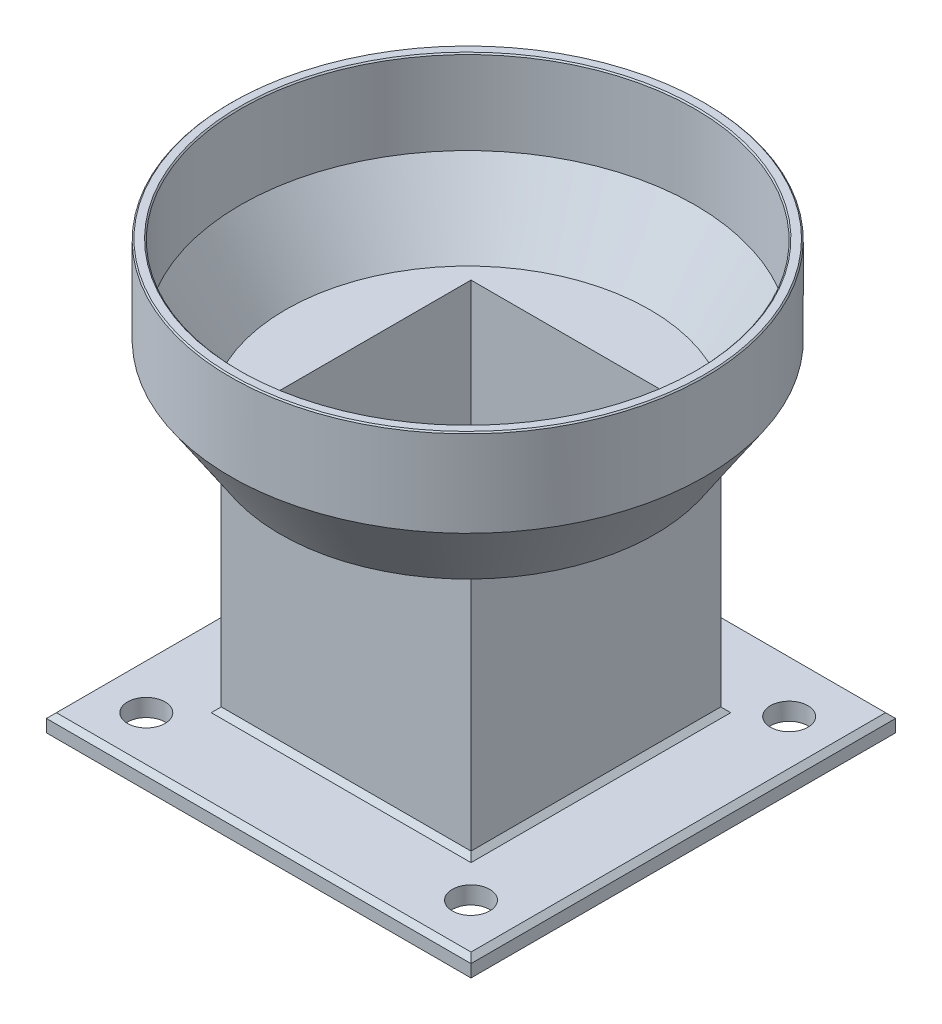
SolidWorks part; units mm, degrees
ref_plane "Plan de face" through (0, 0, 0) normal (0, 0, 1) x (1, 0, 0)
ref_plane "Plan de dessus" through (0, 0, 0) normal (0, 1, 0) x (1, 0, 0)
ref_plane "Plan de droite" through (0, 0, 0) normal (1, 0, 0) x (0, 0, -1)
sketch "Esquisse1" plane through (0, 0, 0) normal (0, 1, 0) x (1, 0, 0)
  line L13 (-124.8507, 26.306) -> (45.1493, 26.306)
  line L14 (-124.8507, 26.306) -> (-124.8507, -143.694)
  line L15 (-124.8507, -143.694) -> (45.1493, -143.694)
  line L16 (45.1493, 26.306) -> (45.1493, -143.694)
  dimension "D1" = 170
  dimension "D2" = 170
extrude "Boss.-Extru.1" add sketch "Esquisse1" along normal blind 7
sketch "Esquisse2" plane through (0, 7, 0) normal (0, 1, 0) x (1, 0, 0)
  line L0 (-124.8507, 26.306) -> (-124.8507, -143.694) construction
  line L1 (-89.8507, -8.694) -> (10.1493, -8.694)
  line L2 (-89.8507, -8.694) -> (-89.8507, -108.694)
  line L3 (-89.8507, -108.694) -> (10.1493, -108.694)
  line L4 (10.1493, -8.694) -> (10.1493, -108.694)
  line L5 (45.1493, 26.306) -> (-124.8507, 26.306) construction
  dimension "D1" = 100
  dimension "D2" = 100
  dimension "D3" = 35
  dimension "D4" = 35
extrude "Boss.-Extru.2" add sketch "Esquisse2" along normal blind 100
ref_plane "Plan1" through (0, 0, 60) normal (0, 0, 1) x (1, 0, 0)
sketch "Esquisse3" plane through (0, 0, 60) normal (0, 0, 1) x (1, 0, 0)
  line L1 (55.1493, 137) -> (55.1493, 172)
  line L2 (55.1493, 172) -> (-39.8507, 172)
  line L3 (-39.8507, 172) -> (-39.8507, 107)
  line L4 (-89.8507, 107) -> (10.1493, 107) construction
  line L6 (-39.8507, 107) -> (35.1493, 107)
  line L7 (35.1493, 107) -> (55.1493, 137)
  point P0 (55.1493, 130.3074)
  dimension "D1" = 95
  dimension "D2" = 75
  dimension "D3" = 65
  dimension "D4" = 35
revolve "Révolution1" add sketch "Esquisse3" angle 360 about L3
shell "Coque1" thickness 4 removed face at (-134.8507, 172, 60)
chamfer "Chanfrein1" distance 2 angle 45 8 edges at (-39.8507, 7, -26.306) (45.1493, 7, 58.694) (-39.8507, 7, 143.694) (-124.8507, 7, 58.694) (-39.8507, 7, 108.694) (10.1493, 7, 58.694) (-39.8507, 7, 8.694) (-89.8507, 7, 58.694)
chamfer "Chanfrein2" distance 0.5 angle 45 2 edges at (-134.8507, 172, 60) (51.1493, 172, 60)
sketch "Esquisse4" plane through (0, 7, 0) normal (0, 1, 0) x (1, 0, 0)
  line L0 (43.1493, -141.694) -> (43.1493, 24.306) construction
  line L1 (-122.8507, -141.694) -> (43.1493, -141.694) construction
  line L2 (-55, -60) -> (55, -60) construction
  line L3 (-122.8507, 24.306) -> (-122.8507, -141.694) construction
  circle A0 centre (25.1493, -123.694) radius 7.5
  circle A1 centre (25.1493, 3.694) radius 7.5
  circle A2 centre (-104.8507, -123.694) radius 7.5
  circle A3 centre (-104.8507, 3.694) radius 7.5
  dimension "D1" = 18
  dimension "D2" = 18
  dimension "D3" = 15
  dimension "D4" = 18
  dimension "D5" = 18
extrude "Enlèv. mat.-Extru.1" cut sketch "Esquisse4" against normal blind 70
